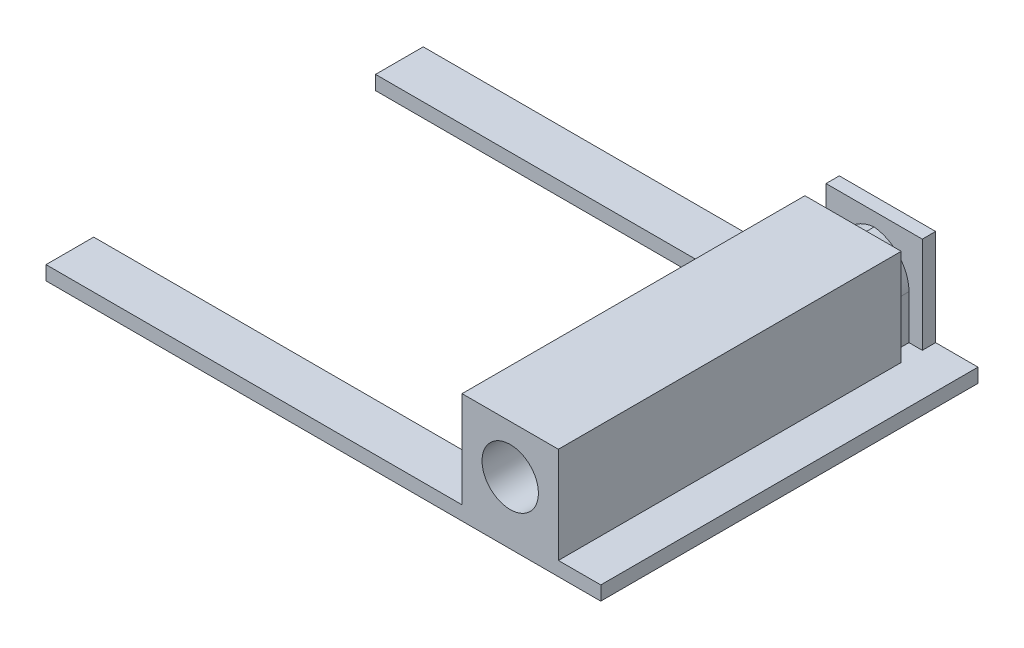
SolidWorks part; units mm, degrees
ref_plane "Front Plane" through (0, 0, 0) normal (0, 0, 1) x (1, 0, 0)
ref_plane "Top Plane" through (0, 0, 0) normal (0, 1, 0) x (1, 0, 0)
ref_plane "Right Plane" through (0, 0, 0) normal (1, 0, 0) x (0, 0, -1)
sketch "Sketch1" plane through (0, 0, 0) normal (0, 1, 0) x (1, 0, 0)
  line L0 (-367.7462, 196.8254) -> (132.2538, 196.8254)
  line L1 (132.2538, 196.8254) -> (132.2538, -143.1746)
  line L2 (132.2538, -143.1746) -> (-367.7462, -143.1746)
  line L3 (-484.8034, -57.1746) -> (-117.7462, -143.1746) construction
  line L4 (0.1966, 110.8254) -> (-367.7462, -143.1746) construction
  line L5 (-301.2748, -100.1746) -> (-367.7462, -100.1746) construction
  line L6 (0.1966, 110.8254) -> (132.2538, -143.1746) construction
  line L7 (-367.7462, -100.1746) -> (132.2538, -100.1746) construction
  line L8 (-367.7462, 196.8254) -> (0.1966, 110.8254) construction
  line L9 (-117.7462, 196.8254) -> (-484.8034, -57.1746) construction
  line L10 (-183.7748, 153.8254) -> (-367.7462, 153.8254) construction
  line L11 (0.1966, 110.8254) -> (132.2538, 196.8254) construction
  line L12 (-183.7748, 153.8254) -> (132.2538, 153.8254) construction
  line L13 (-367.7462, 196.8254) -> (-367.7462, 153.8254)
  line L14 (-117.7462, 196.8254) -> (132.2538, 153.8254) construction
  line L15 (132.2538, 196.8254) -> (0, 153.8254) construction
  line L16 (132.2538, -143.1746) -> (-267.7462, -143.1746) construction
  line L17 (7.2538, 175.3254) -> (7.2538, -100.1746) construction
  line L18 (-367.7462, 153.8254) -> (7.2538, 153.8254) construction
  line L19 (7.2538, 153.8254) -> (7.2538, -100.1746) construction
  line L20 (-367.7462, 153.8254) -> (7.2538, 153.8254)
  line L21 (7.2538, 153.8254) -> (7.2538, -100.1746)
  line L22 (7.2538, -100.1746) -> (-367.7462, -100.1746)
  line L23 (-367.7462, -100.1746) -> (-367.7462, -143.1746)
  line L24 (132.2538, -143.1746) -> (-67.7462, -143.1746) construction
  line L25 (-67.7462, -143.1746) -> (-67.7462, 196.8254) construction
  line L27 (75.0538, 48.3254) -> (49.6538, 48.3254) construction
  line L28 (49.6538, 48.3254) -> (24.2538, 48.3254) construction
  point P15 (-67.7462, 26.8254)
  dimension "D1" = 43
  dimension "D2" = 500
  dimension "D3" = 340
  dimension "D4" = 485
  dimension "D5" = 400
  dimension "D6" = 200
  dimension "D7" = 50.8
  dimension "D8" = 17
extrude "Boss-Extrude1" add sketch "Sketch1" along normal blind 12.7 contours L22 L23 L2 L1 L0 L13 L20 L21
ref_plane "Plane1" through (0, 12.7, 0) normal (0, 1, 0) x (1, 0, 0)
sketch "Sketch3" plane through (0, 12.7, 0) normal (0, 1, 0) x (1, 0, 0)
  line L0 (7.2538, 26.8254) -> (25.2538, 26.8254) construction
  line L1 (7.2538, 153.8254) -> (7.2538, -100.1746) construction
  line L2 (25.2538, 26.8254) -> (76.0538, 26.8254) construction
  line L3 (76.0538, 26.8254) -> (94.0538, 26.8254) construction
  line L4 (50.6538, 26.8254) -> (50.6538, -143.1746) construction
  line L5 (132.2538, -143.1746) -> (-367.7462, -143.1746) construction
  line L6 (50.6538, 26.8254) -> (50.6538, 196.8254) construction
  line L7 (-367.7462, 196.8254) -> (132.2538, 196.8254) construction
  line L8 (94.0538, 26.8254) -> (94.0538, 196.8254) construction
  line L9 (7.2538, 196.8254) -> (7.2538, -143.1746) construction
  line L10 (94.0538, 26.8254) -> (94.0538, -143.1746) construction
  line L11 (25.2538, 26.8254) -> (25.2538, 196.8254) construction
  line L12 (76.0538, 196.8254) -> (76.0538, -143.1746) construction
  line L13 (25.2538, 26.8254) -> (25.2538, -143.1746) construction
  dimension "D1" = 18
  dimension "D2" = 18
  dimension "D3" = 50.8
ref_plane "Plane2" through (0, 0, 143.1746) normal (0, 0, 1) x (1, 0, 0)
sketch "Sketch4" plane through (0, 0, 143.1746) normal (0, 0, 1) x (1, 0, 0)
  line L0 (132.2538, 12.7) -> (-367.7462, 12.7) construction
  line L1 (7.2538, 12.7) -> (94.0538, 12.7)
  line L2 (7.2538, 12.7) -> (7.2538, 99.5)
  line L3 (7.2538, 99.5) -> (94.0538, 99.5)
  line L4 (94.0538, 12.7) -> (94.0538, 99.5)
  line L5 (7.2538, 12.7) -> (94.0538, 99.5) construction
  line L6 (94.0538, 12.7) -> (7.2538, 99.5) construction
  line L7 (25.2538, 12.7) -> (25.2538, 99.5) construction
  circle A0 centre (50.6538, 56.1) radius 25.4
ref_plane "Plane3" through (0, 0, -196.8254) normal (0, 0, -1) x (-1, 0, 0)
extrude "Boss-Extrude3" add sketch "Sketch4" against normal up to vertex (340 mm away) up to point (132.2538, 12.7, -196.8254)
ref_plane "Plane4" through (0, 99.5, 0) normal (0, 1, 0) x (1, 0, 0)
sketch "Sketch6" plane through (0, 99.5, 0) normal (0, 1, 0) x (1, 0, 0)
  line L0 (7.2538, 196.8254) -> (7.2538, 153.8254) construction
  line L1 (7.2538, 153.8254) -> (94.0538, 196.8254) construction
  line L2 (7.2538, 153.8254) -> (94.0538, 153.8254) construction
  line L3 (94.0538, 26.8254) -> (94.0538, 196.8254) construction
  line L4 (94.0538, 153.8254) -> (50.6538, 175.3254) construction
  line L5 (50.6538, 175.3254) -> (7.2538, 196.8254) construction
  line L6 (94.0538, 196.8254) -> (94.0538, 184.8254) construction
  line L7 (94.0538, 184.8254) -> (7.2538, 184.8254) construction
  line L8 (94.0538, 153.8254) -> (94.0538, 165.8254) construction
  line L10 (94.0538, 165.8254) -> (7.2538, 165.8254) construction
  line L12 (7.2538, 184.8254) -> (94.0538, 184.8254)
  line L13 (7.2538, 184.8254) -> (7.2538, 165.8254)
  line L14 (7.2538, 165.8254) -> (94.0538, 165.8254)
  line L15 (94.0538, 184.8254) -> (94.0538, 165.8254)
  dimension "D1" = 12
extrude "Cut-Extrude3" cut sketch "Sketch6" against normal blind 12
ref_plane "Plane9" through (7.2538, 0, 0) normal (-1, 0, 0) x (0, 0, 1)
sketch "Sketch7" plane through (7.2538, 0, 0) normal (-1, 0, 0) x (0, 0, 1)
  line L0 (-184.8254, 87.5) -> (-184.8254, 12.7) construction
  line L1 (-196.8254, 12.7) -> (143.1746, 12.7) construction
  line L2 (-165.8254, 87.5) -> (-165.8254, 12.7) construction
  line L4 (-184.8254, 87.5) -> (-165.8254, 87.5)
  line L5 (-184.8254, 87.5) -> (-184.8254, 12.7)
  line L6 (-184.8254, 12.7) -> (-165.8254, 12.7)
  line L7 (-165.8254, 87.5) -> (-165.8254, 12.7)
extrude "Cut-Extrude4" cut sketch "Sketch7" against normal blind 12 contours L5 L6 L7 L4
ref_plane "Plane10" through (94.0538, 0, 0) normal (1, 0, 0) x (0, 0, -1)
sketch "Sketch8" plane through (94.0538, 0, 0) normal (1, 0, 0) x (0, 0, -1)
  line L0 (184.8254, 87.5) -> (184.8254, 12.7) construction
  line L1 (26.8254, 12.7) -> (196.8254, 12.7) construction
  line L3 (165.8254, 87.5) -> (184.8254, 87.5)
  line L4 (165.8254, 87.5) -> (165.8254, 12.7)
  line L5 (165.8254, 12.7) -> (184.8254, 12.7)
  line L6 (184.8254, 87.5) -> (184.8254, 12.7)
extrude "Cut-Extrude5" cut sketch "Sketch8" against normal blind 12
fillet "Fillet2" radius 35 2 edges at (82.0538, 87.5, -175.3254) (19.2538, 87.5, -175.3254)
